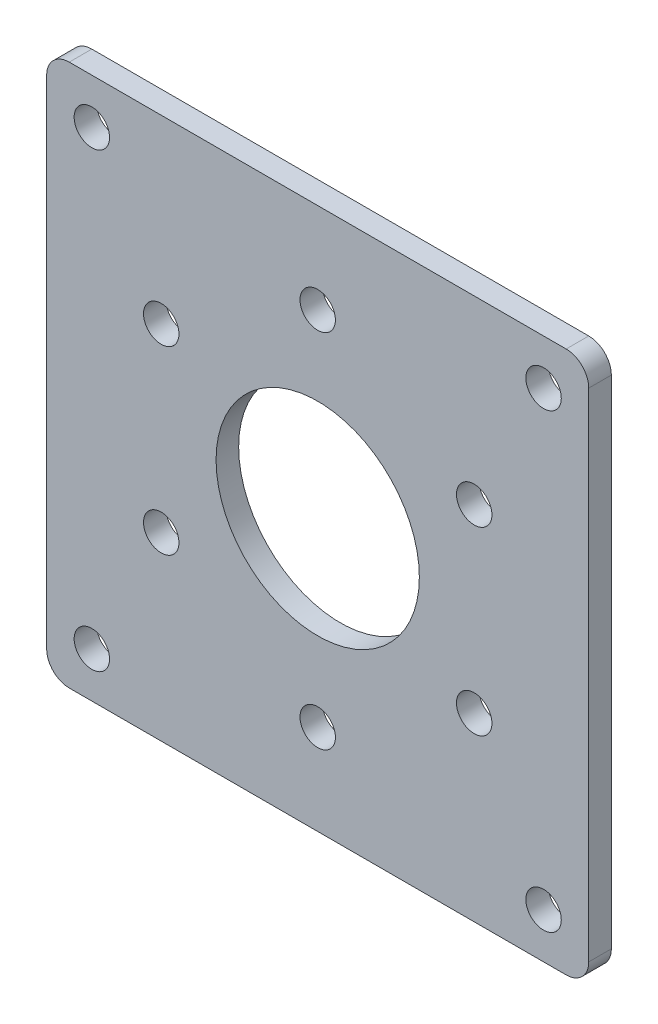
SolidWorks part; units mm, degrees
material "6061-T6 (SS)"
ref_plane "Front Plane" through (0, 0, 0) normal (0, 0, 1) x (1, 0, 0)
ref_plane "Top Plane" through (0, 0, 0) normal (0, 1, 0) x (1, 0, 0)
ref_plane "Right Plane" through (0, 0, 0) normal (1, 0, 0) x (0, 0, -1)
sketch "Sketch1" plane through (0, 0, 0) normal (0, 0, 1) x (1, 0, 0)
  line L0 (-31.75, -31.75) -> (-31.75, 31.75) construction
  line L1 (-38.1, -38.1) -> (38.1, -38.1)
  line L2 (-38.1, -38.1) -> (-38.1, 38.1)
  line L3 (-38.1, 38.1) -> (38.1, 38.1)
  line L4 (38.1, -38.1) -> (38.1, 38.1)
  line L5 (-38.1, -38.1) -> (38.1, 38.1) construction
  line L6 (-38.1, 38.1) -> (38.1, -38.1) construction
  line L7 (-31.75, 31.75) -> (31.75, 31.75) construction
  line L8 (31.75, -31.75) -> (31.75, 31.75) construction
  line L9 (-31.75, -31.75) -> (31.75, -31.75) construction
  circle A0 centre (0, 0) radius 30
  circle A1 centre (0, 25.4) radius 2.4892
  circle A2 centre (0, 0) radius 25.4 construction
  circle A3 centre (21.997, 12.7) radius 2.4892
  circle A4 centre (21.997, -12.7) radius 2.4892
  circle A5 centre (0, -25.4) radius 2.4892
  circle A6 centre (-21.997, -12.7) radius 2.4892
  circle A7 centre (-21.997, 12.7) radius 2.4892
  circle A8 centre (0, 0) radius 14.2875
  circle A9 centre (-31.75, 31.75) radius 2.4892
  circle A10 centre (-31.75, -31.75) radius 2.4892
  circle A11 centre (31.75, -31.75) radius 2.4892
  circle A12 centre (31.75, 31.75) radius 2.4892
  point P0 (0, 0)
  point P24 (0, 0)
  dimension "D1" = 60
  dimension "D2" = 4.9784
  dimension "D3" = 50.8
  dimension "D6" = 28.575
  dimension "D8" = 4.9784
  dimension "D5" = 76.2
  dimension "D7" = 6.35
  dimension "D4" = 6
extrude "Boss-Extrude1" add sketch "Sketch1" along normal blind 3.175 contours L1 L4 L3 L2 A12 A11 A10 A9 A0 | A0 A8 A7 A6 A5 A4 A3 A1 region at (-37.0224, 0, 0) region at (-29.1515, 0, 0)
fillet "Fillet1" radius 3.175 4 edges at (-38.1, -38.1, 1.5875) (38.1, 38.1, 1.5875) (38.1, -38.1, 1.5875) (-38.1, 38.1, 1.5875)
